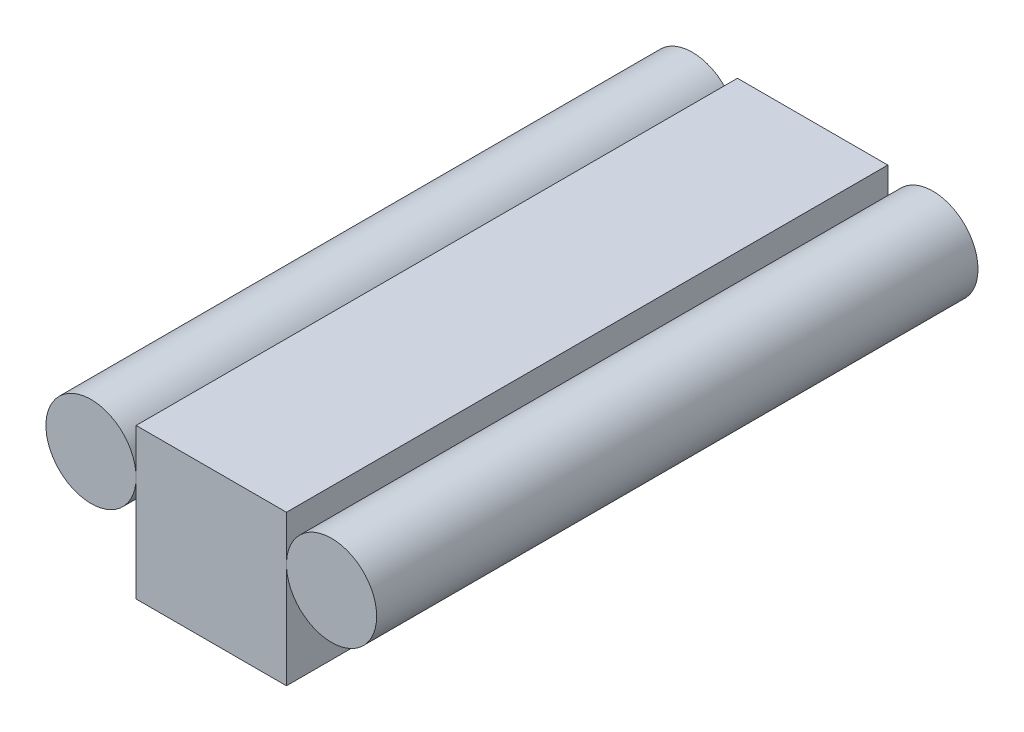
SolidWorks part; units mm, degrees
ref_plane "Front Plane" through (0, 0, 0) normal (0, 0, 1) x (1, 0, 0)
ref_plane "Top Plane" through (0, 0, 0) normal (0, 1, 0) x (1, 0, 0)
ref_plane "Right Plane" through (0, 0, 0) normal (1, 0, 0) x (0, 0, -1)
sketch "Sketch1" plane through (0, 0, 0) normal (0, 0, 1) x (1, 0, 0)
  line L1 (0, 101.5687) -> (-500, 101.5687)
  line L2 (0, 101.5687) -> (0, -398.4313)
  line L3 (0, -398.4313) -> (-500, -398.4313)
  line L4 (-500, 101.5687) -> (-500, -398.4313)
  circle A0 centre (-650, -48.4313) radius 150
  circle A3 centre (150, -48.4313) radius 150
  dimension "D2" = 300
  dimension "D4" = 300
  dimension "D1" = 500
  dimension "D3" = 500
extrude "Boss-Extrude2" add sketch "Sketch1" along normal blind 2000 contours A0 | A3 | L1 L4 L3 L2 region at (-250, -148.4313, 0) region at (150, -48.4313, 0) region at (-650, -48.4313, 0)
